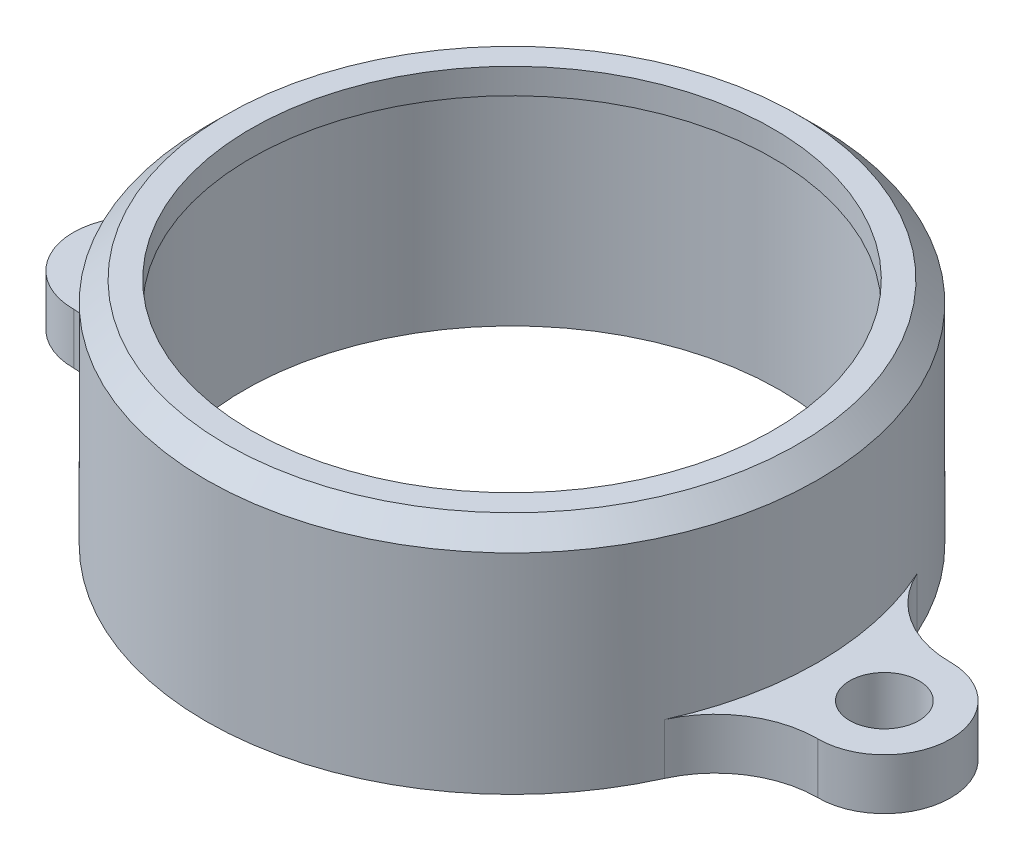
SolidWorks part; units mm, degrees
material "ABS PC"
ref_plane "Front Plane" through (0, 0, 0) normal (0, 0, 1) x (1, 0, 0)
ref_plane "Top Plane" through (0, 0, 0) normal (0, 1, 0) x (1, 0, 0)
ref_plane "Right Plane" through (0, 0, 0) normal (1, 0, 0) x (0, 0, -1)
sketch "Sketch1" plane through (0, 0, 0) normal (0, 1, 0) x (1, 0, 0)
  circle A0 centre (0, 0) radius 16.256
  circle A1 centre (0, 0) radius 19.05
  dimension "D1" = 32.512
  dimension "D2" = 38.1
extrude "Boss-Extrude1" add sketch "Sketch1" against normal blind 1.5875
sketch "Sketch2" plane through (0, -1.5875, 0) normal (0, -1, 0) x (1, 0, 0)
  circle A0 centre (0, 0) radius 19.05
  circle A1 centre (0, 0) radius 16.6687
  dimension "D1" = 38.1
  dimension "D2" = 2.3813
extrude "Boss-Extrude2" add sketch "Sketch2" along normal up to surface (9.525 mm away)
chamfer "Chamfer1" distance 1.27 angle 45 1 edges at (0, 0, 19.05)
sketch "Sketch3" plane through (0, -11.1125, 0) normal (0, -1, 0) x (1, 0, 0)
  line L0 (-23.1775, 4.1275) -> (-18.5975, 4.1275)
  line L1 (-23.1775, -4.1275) -> (-18.5975, -4.1275)
  line L4 (0, 16.6687) -> (0, -16.6687) construction
  line L5 (23.1775, -4.1275) -> (18.5975, -4.1275)
  line L6 (23.1775, 4.1275) -> (18.5975, 4.1275)
  circle A0 centre (0, 0) radius 19.05 construction
  circle A1 centre (0, 0) radius 16.6687 construction
  arc A2 (-18.5975, -4.1275) -> (18.5975, -4.1275) centre (0, 0) ccw
  circle A3 centre (0, 0) radius 16.6687
  arc A4 (-23.1775, 4.1275) -> (-23.1775, -4.1275) centre (-23.1775, 0) ccw
  arc A5 (18.5975, 4.1275) -> (-18.5975, 4.1275) centre (0, 0) ccw
  arc A6 (23.1775, 4.1275) -> (23.1775, -4.1275) centre (23.1775, 0) cw
  dimension "D1" = 8.255
extrude "Boss-Extrude3" add sketch "Sketch3" along normal blind 3.175
fillet "Fillet1" radius 6.35 4 edges at (-18.5975, -12.7, -4.1275) (18.5975, -12.7, -4.1275) (18.5975, -12.7, 4.1275) (-18.5975, -12.7, 4.1275)
hole_wizard "#6 Clearance Hole1" positions "Sketch6" profile "Sketch7" hole size "#6" standard "ANSI Inch" end condition up to next
sketch "Sketch6" plane through (0, -14.2875, 0) normal (0, -1, 0) x (-1, 0, 0)
  point P0 (-23.1775, 0)
  point P3 (23.1775, 0)
sketch "Sketch7" plane through (23.1775, -14.2875, 0) normal (1, 0, 0) x (0, 0, -1)
  line L0 (0, 0) -> (0, 3.175)
  line L1 (0, 3.175) -> (2.1526, 3.175)
  line L2 (2.1526, 3.175) -> (2.1526, 0)
  line L5 (2.1526, 0) -> (0, 0)
  line L11 (0, -6.35) -> (0, 107.95) construction
  dimension "Thru Hole Dia." = 4.3053
  dimension "Thru Hole Depth" = 3.175
